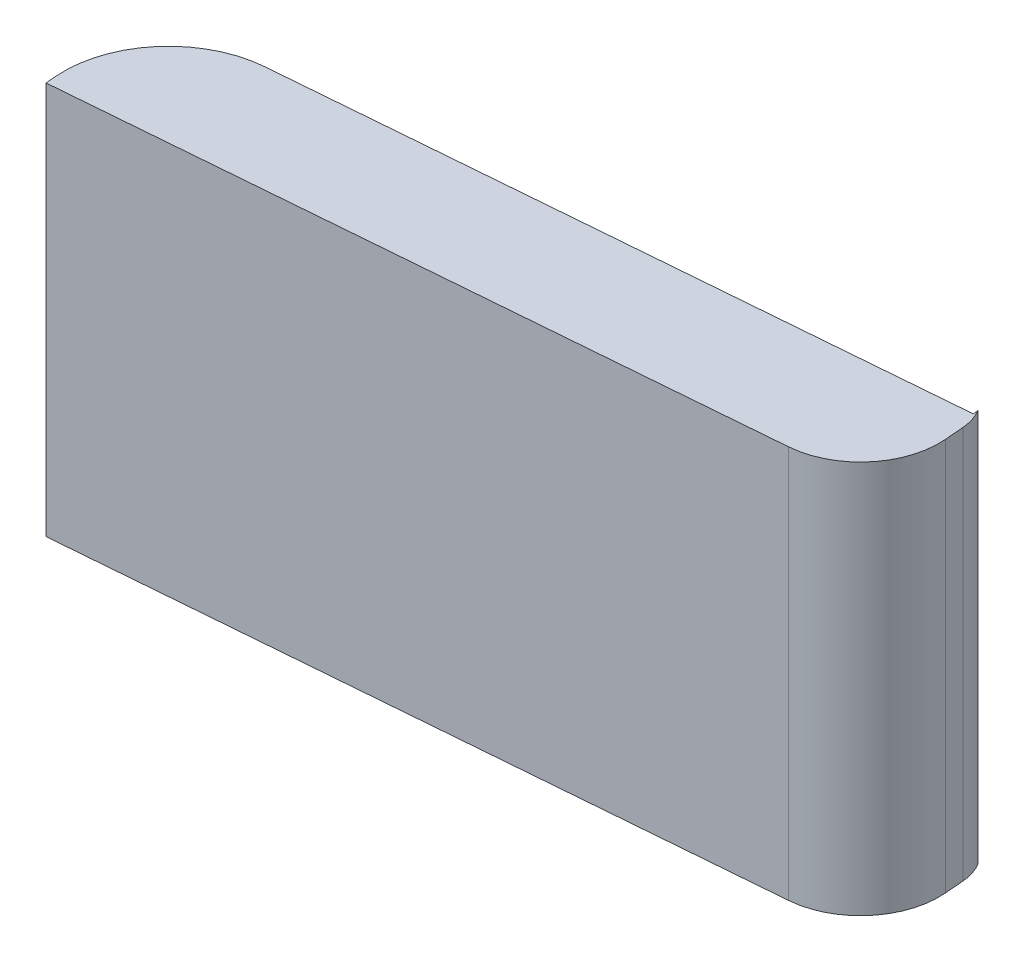
SolidWorks part; units mm, degrees
ref_plane "Front Plane" through (0, 0, 0) normal (0, 0, 1) x (1, 0, 0)
ref_plane "Top Plane" through (0, 0, 0) normal (0, 1, 0) x (1, 0, 0)
ref_plane "Right Plane" through (0, 0, 0) normal (1, 0, 0) x (0, 0, -1)
sketch "Sketch2" plane through (0, 0, 0) normal (0, 1, 0) x (1, 0, 0)
  line L0 (-30.9651, -2.5653) -> (-320.9651, -26.3075)
  dimension "D1" = 290
extrude "Extrude-Thin1" add sketch "Sketch2" along normal blind 150 thin thin type one direction wall 2
sketch "Sketch5" plane through (0.0025, 0, 0.03) normal (-0.0816, 0, -0.9967) x (-0.9967, 0, 0.0816)
  line L0 (322.0414, 0) -> (31.0712, 0)
  line L1 (31.0712, 150) -> (322.0414, 150)
  line L6 (322.0414, 150) -> (322.0414, 0) construction
  line L7 (322.0414, 150) -> (31.0712, 150) construction
extrude "Extrude-Thin2" add sketch "Sketch5" along normal blind 42 separate body thin
fillet "Fillet6" radius 40 1 edges at (-324.3922, 148, -15.5524)
sketch "Sketch11" plane through (0, 146, 0) normal (0, -1, 0) x (1, 0, 0)
  line L9 (-321.1283, 24.3142) -> (-320.9651, 26.3075)
  line L11 (-284.5256, -18.8163) -> (-281.9366, -19.588)
  line L12 (-284.5256, -18.8163) -> (-290.8059, -18.2387)
  line L13 (-290.8059, -18.2387) -> (-291.7983, -17.537)
  line L14 (-291.7983, -17.537) -> (-298.2881, -15.145)
  line L15 (-298.2881, -15.145) -> (-304.2542, -11.6811)
  line L17 (-304.2542, -11.6811) -> (-309.5289, -7.251)
  line L18 (-309.5289, -7.251) -> (-313.8101, -2.2005)
  line L19 (-313.8101, -2.2005) -> (-317.4664, 4.0439)
  line L20 (-317.4664, 4.0439) -> (-318.3453, 5.6969)
  line L21 (-318.3453, 5.6969) -> (-319.8616, 10.5601)
  line L22 (-319.8616, 10.5601) -> (-321.0892, 17.34)
  line L23 (-321.0892, 17.34) -> (-321.1283, 24.3142)
  line L24 (-281.9366, -19.588) -> (-278.0031, -19.3503)
  line L25 (-34.3922, -39.2947) -> (-284.5256, -18.8163) construction
  arc A0 (-321.1283, 24.3142) -> (-284.5256, -18.8163) centre (-281.2617, 21.0503) ccw construction
  arc A4 (-321.1283, 24.3142) -> (-284.5256, -18.8163) centre (-281.2617, 21.0503) ccw construction
extrude "Extrude-Thin7" add sketch "Sketch11" along normal blind 146 thin
fillet "Fillet14" radius 40 1 edges at (-324.3922, 2, -15.5524)
sketch "Sketch25" plane through (-30.9676, 0, 2.5353) normal (0.9967, 0, -0.0816) x (-0.0816, 0, -0.9967)
  line L0 (41.9699, 0) -> (41.9699, 4) construction
  line L1 (43.9699, 150) -> (-2.0301, 150)
  line L2 (43.9699, 150) -> (43.9699, 0)
  line L3 (43.9699, 0) -> (-2.0301, 0)
  line L4 (-2.0301, 150) -> (-2.0301, 0)
  dimension "D1" = 2
extrude "Boss-Extrude1" add sketch "Sketch25" along normal blind 2
fillet "Fillet22" radius 30 1 edges at (-30.9651, 75, 2.5653)
fillet "Fillet28" radius 30 1 edges at (-28.8086, 75, 4.3954)
fillet "Fillet32" radius 20 1 edges at (-32.562, 75, -41.4512)
sketch "Sketch29" plane through (0.0025, 0, 0.03) normal (-0.0816, 0, -0.9967) x (-0.9967, 0, 0.0816)
  line L0 (61.0712, 146) -> (320.0414, 146) construction
  line L1 (153.7548, 146) -> (147.2438, 146)
  line L2 (153.7548, 146) -> (153.7548, 141.9431)
  line L3 (153.7548, 141.9431) -> (147.2438, 141.9431)
  line L4 (147.2438, 146) -> (147.2438, 141.9431)
extrude "Boss-Extrude2" add sketch "Sketch29" along normal blind 42
sketch "Sketch35" plane through (0, 146, 0) normal (0, -1, 0) x (1, 0, 0)
  line L0 (-34.3922, -39.2947) -> (-38.9415, -38.9222)
  line L1 (-34.3922, -39.2947) -> (-150.1774, -29.8154) construction
extrude "Extrude-Thin8" add sketch "Sketch35" along normal up to surface (142 mm away) thin
